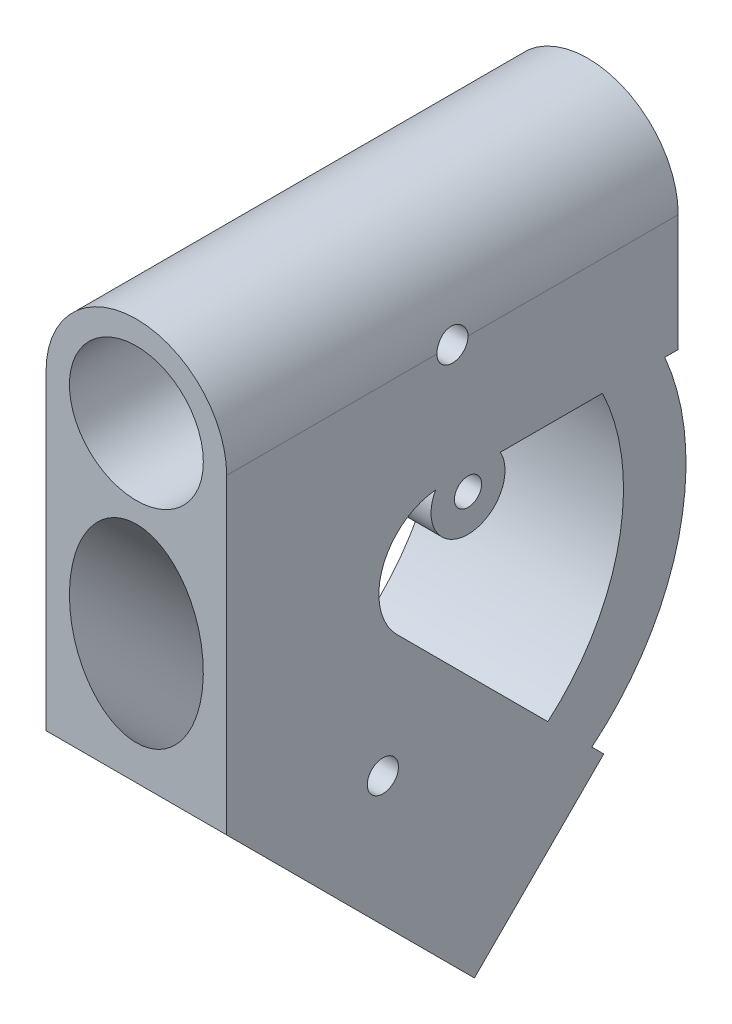
SolidWorks part; units mm, degrees
ref_plane "Alzado" through (0, 0, 0) normal (0, 0, 1) x (1, 0, 0)
ref_plane "Planta" through (0, 0, 0) normal (0, 1, 0) x (1, 0, 0)
ref_plane "Vista lateral" through (0, 0, 0) normal (1, 0, 0) x (0, 0, -1)
sketch "Croquis1" plane through (0, 0, 0) normal (0, 0, 1) x (1, 0, 0)
  line L0 (0, 0) -> (0, -15) construction
  line L1 (-11.6, -15) -> (11.6, -15)
  line L2 (-11.6, -15) -> (-11.6, 0)
  line L3 (11.6, -15) -> (11.6, 0)
  circle A0 centre (0, 0) radius 8.6
  arc A1 (11.6, 0) -> (-11.6, 0) centre (0, 0) ccw
  point P8 (0, -15)
  dimension "D1" = 17.2
  dimension "D2" = 3
  dimension "D3" = 15
extrude "Saliente-Extruir1" add sketch "Croquis1" against normal mid plane 58
ref_plane "Plano1" through (0, -15, 0) normal (0, -1, 0) x (-1, 0, 0)
sketch "Croquis2" plane through (0, 0, 0) normal (1, 0, 0) x (0, 0, -1)
  line L0 (-29, -15) -> (-29, -40)
  line L1 (-29, -40) -> (2.8198, -71.8198)
  line L4 (29, -15) -> (-29, -15) construction
  line L5 (2.8198, -71.8198) -> (19.4368, -55.2028)
  line L6 (11.1283, -63.5113) -> (-29, -23.383) construction
  line L7 (-29, -15) -> (-1.4523, -15)
  line L8 (-7.1091, -28.6569) -> (19.4368, -55.2028)
  arc A0 (-7.1091, -28.6569) -> (-1.4523, -15) centre (-1.4523, -23) cw
  dimension "D3" = 8
  dimension "D1" = 135
  dimension "D2" = 23.5
  dimension "D4" = 45
  dimension "D5" = 25
extrude "Saliente-Extruir2" add sketch "Croquis2" along normal mid plane 23.2
ref_plane "Plano3" through (0, -37.3198, -37.3198) normal (0, -0.7071, -0.7071) x (-1, 0, 0)
sketch "Croquis4" plane through (0, -37.3198, -37.3198) normal (0, -0.7071, -0.7071) x (-1, 0, 0)
  line L0 (0, -25.2904) -> (0, -48.7904) construction
  line L1 (-11.6, -25.2904) -> (11.6, -25.2904) construction
  line L2 (-11.6, -48.7904) -> (11.6, -48.7904) construction
  circle A0 centre (0, -37.0404) radius 8.6
  dimension "D1" = 17.2
extrude "Cortar-Extruir1" cut sketch "Croquis4" against normal blind 80
sketch "Croquis7" plane through (0, 0, 0) normal (1, 0, 0) x (0, 0, -1)
  line L0 (19.4368, -55.2028) -> (-7.1091, -28.6569) construction
  line L1 (29, -15) -> (29, 0) construction
  line L2 (2.8198, -71.8198) -> (19.4368, -55.2028) construction
  line L3 (29, -15) -> (-1.4523, -15) construction
  line L4 (19.2702, -15) -> (27.2702, -15)
  line L5 (12.2509, -48.0169) -> (17.9078, -53.6738)
  arc A0 (12.2509, -48.0169) -> (19.2702, -15) centre (-5.7469, -26.9361) ccw
  arc A1 (27.2702, -15) -> (17.9078, -53.6738) centre (-3, -28.1421) cw
  dimension "D1" = 8
  dimension "D3" = 3
  dimension "D4" = 32
  dimension "D5" = 35
  dimension "D6" = 33
  dimension "D2" = 8
extrude "Saliente-Extruir3" add sketch "Croquis7" along normal mid plane 23.2
sketch "Croquis8" plane through (0, 0, 0) normal (1, 0, 0) x (0, 0, -1)
  line L0 (-29, 0) -> (-29, -40) construction
  circle A0 centre (2, -17.3114) radius 1.75
  circle A1 centre (2, -17.3114) radius 4.75
  dimension "D1" = 3
  dimension "D2" = 3.5
  dimension "D3" = 31
extrude "Saliente-Extruir4" add sketch "Croquis8" along normal mid plane 23.2
sketch "Croquis9" plane through (0, 0, 0) normal (1, 0, 0) x (0, 0, -1)
  circle A0 centre (24.5509, -21.7313) radius 1.6
  circle A1 centre (20.1094, -44.2984) radius 1.6
  circle A2 centre (2, -17.3114) radius 1.75 construction
  dimension "D1" = 3.2
  dimension "D2" = 22.98
  dimension "D3" = 32.5
  dimension "D4" = 23
extrude "Cortar-Extruir2" cut sketch "Croquis9" against normal mid plane 21
sketch "Croquis10" plane through (0, 0, 0) normal (1, 0, 0) x (0, 0, -1)
  line L0 (29, 0) -> (-29, 0) construction
  line L1 (11.1283, -63.5113) -> (-29, -23.383) construction
  line L2 (2.8198, -71.8198) -> (19.4368, -55.2028) construction
  line L3 (-29, 0) -> (-29, -40) construction
  circle A0 centre (0, 0) radius 2
  circle A1 centre (-8.9358, -43.4471) radius 2
  dimension "D1" = 4
extrude "Cortar-Extruir3" cut sketch "Croquis10" along normal mid plane 40
